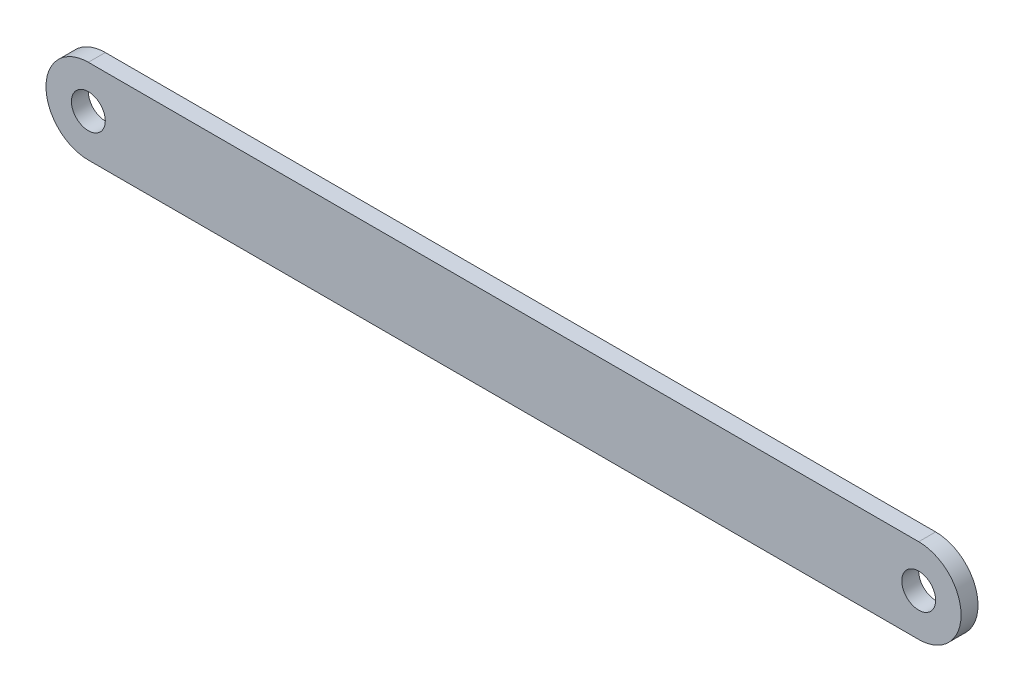
SolidWorks part; units mm, degrees
ref_plane "Front Plane" through (0, 0, 0) normal (0, 0, 1) x (1, 0, 0)
ref_plane "Top Plane" through (0, 0, 0) normal (0, 1, 0) x (1, 0, 0)
ref_plane "Right Plane" through (0, 0, 0) normal (1, 0, 0) x (0, 0, -1)
sketch "Sketch1" plane through (0, 0, 0) normal (0, 0, 1) x (1, 0, 0)
  line L0 (-122.547, 0) -> (122.547, 0) construction
  line L1 (-122.547, 12.5) -> (122.547, 12.5)
  line L2 (-122.547, -12.5) -> (122.547, -12.5)
  arc A0 (-122.547, 12.5) -> (-122.547, -12.5) centre (-122.547, 0) ccw
  arc A1 (122.547, -12.5) -> (122.547, 12.5) centre (122.547, 0) ccw
  point P2 (0, 0)
  dimension "D1" = 245.094
  dimension "D2" = 25
extrude "Boss-Extrude1" add sketch "Sketch1" along normal blind 5 contours A0 L2 A1 L1
hole_wizard "M8 Clearance Hole2" positions "Sketch2" profile "Sketch3" hole size "M8" standard "ANSI Metric" end condition through all
sketch "Sketch2" plane through (0, 0, 5) normal (0, 0, 1) x (1, 0, 0)
  point P0 (-122.547, 0)
sketch "Sketch3" plane through (-122.547, 0, 5) normal (1, 0, 0) x (0, -1, 0)
  line L0 (0, 0) -> (0, 5)
  line L1 (0, 5) -> (5, 5)
  line L2 (5, 5) -> (5, 0)
  line L5 (5, 0) -> (0, 0)
  line L11 (0, -6.35) -> (0, 107.95) construction
  dimension "Thru Hole Dia." = 10
  dimension "Thru Hole Depth" = 5
hole_wizard "M8 Clearance Hole1" positions "Sketch4" profile "Sketch6" hole size "M8" standard "ANSI Metric" end condition through all
sketch "Sketch4" plane through (0, 0, 5) normal (0, 0, 1) x (1, 0, 0)
  point P0 (122.547, 0)
sketch "Sketch6" plane through (122.547, 0, 5) normal (1, 0, 0) x (0, -1, 0)
  line L0 (0, 0) -> (0, 5)
  line L1 (0, 5) -> (5, 5)
  line L2 (5, 5) -> (5, 0)
  line L5 (5, 0) -> (0, 0)
  line L11 (0, -6.35) -> (0, 107.95) construction
  dimension "Thru Hole Dia." = 10
  dimension "Thru Hole Depth" = 5
